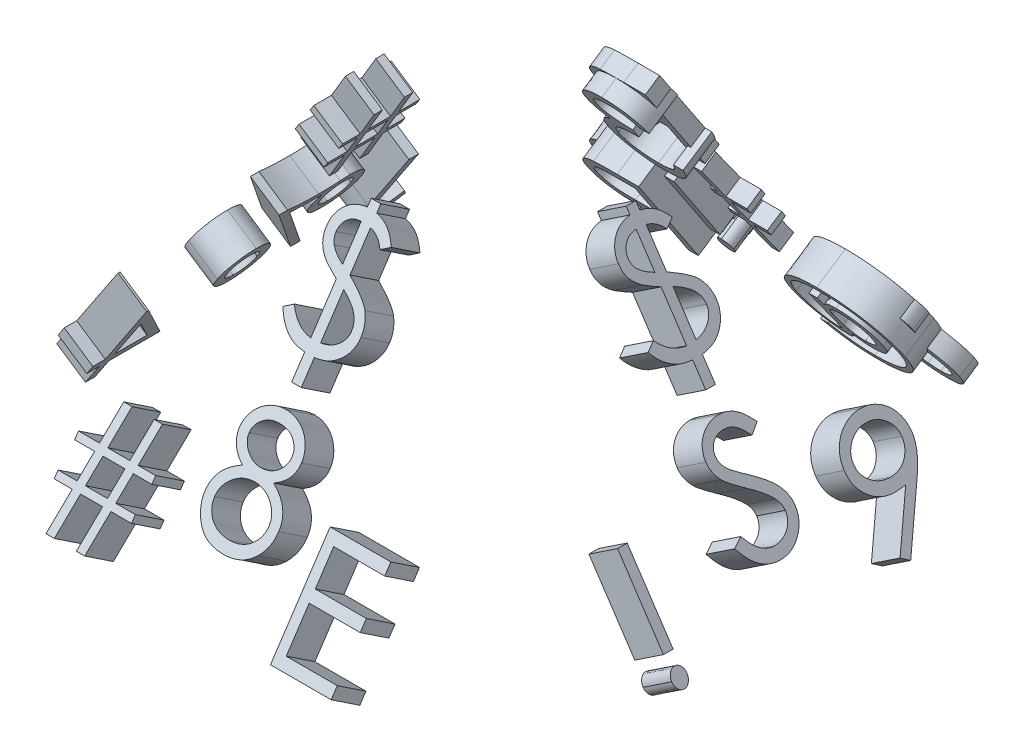
SolidWorks part; units mm, degrees
ref_plane "Front Plane" through (0, 0, 0) normal (0, 0, 1) x (1, 0, 0)
ref_plane "Top Plane" through (0, 0, 0) normal (0, 1, 0) x (1, 0, 0)
ref_plane "Right Plane" through (0, 0, 0) normal (1, 0, 0) x (0, 0, -1)
sketch "Sketch3" plane through (0, 0, 0) normal (0, 1, 0) x (1, 0, 0)
  line L1 (-50.8, -50.8) -> (50.8, -50.8)
  line L2 (-50.8, -50.8) -> (-50.8, 50.8)
  line L3 (-50.8, 50.8) -> (50.8, 50.8)
  line L4 (50.8, -50.8) -> (50.8, 50.8)
  line L5 (-50.8, -50.8) -> (50.8, 50.8) construction
  line L6 (-50.8, 50.8) -> (50.8, -50.8) construction
  point P0 (0, 0)
  dimension "D1" = 101.6
  dimension "D2" = 101.6
ref_plane "Plane4" through (0, 76.2, 0) normal (0, 1, 0) x (1, 0, 0)
sketch "Sketch4" plane through (0, 76.2, 0) normal (0, 1, 0) x (1, 0, 0)
  point P0 (0, 0)
loft "Loft1" add profiles "Sketch4", "Sketch3"
sketch "Sketch7" plane through (0, 23.4462, -35.1692) normal (0, 0.5547, -0.8321) x (-1, 0, 0)
  line L0 (-31.3891, -16.7488) -> (31.3891, -16.7488) construction
  line L1 (31.3891, -16.7488) -> (0, 39.8387) construction
  line L2 (0, 39.8387) -> (-31.3891, -16.7488) construction
  line L3 (0, 63.4022) -> (-50.8, -28.1788) construction
  line L4 (0, 63.4022) -> (50.8, -28.1788) construction
  line L5 (-50.8, -28.1788) -> (50.8, -28.1788) construction
  text T0 "R" font "Century Gothic" height in points 60
  text T1 "9" font "Century Gothic" height in points 60
  text T2 "&" font "Century Gothic" height in points 60
  text T3 "#" font "Century Gothic" height in points 60
  point P21 (0, 0)
  dimension "D1" = 11.43
  dimension "D2" = 11.43
  dimension "D3" = 11.43
  dimension "D4" = 22.86
  dimension "D5" = 6.35
  dimension "D6" = 0
  dimension "D7" = 17.78
  dimension "D8" = 0
  dimension "D9" = 4.318
  dimension "D10" = 3.81
  dimension "D11" = 7.62
shell "Shell2" thickness 2.54 removed face at (0, 0, 0)
sketch "Sketch8" plane through (0, 0, 0) normal (0, -1, 0) x (1, 0, 0)
  line L1 (47.7473, -47.7473) -> (-47.7473, -47.7473)
  line L2 (47.7473, -47.7473) -> (47.7473, 47.7473)
  line L3 (47.7473, 47.7473) -> (-47.7473, 47.7473)
  line L4 (-47.7473, -47.7473) -> (-47.7473, 47.7473)
extrude "Boss-Extrude1" add sketch "Sketch8" against normal blind 2.54
sketch "Sketch9" plane through (0, 23.4462, -35.1692) normal (0, 0.5547, -0.8321) x (-1, 0, 0)
  line L0 (-50.8, -28.1788) -> (50.8, -28.1788) construction
  circle A0 centre (35.4584, -19.2888) radius 5.715
  dimension "D1" = 11.43
  dimension "D2" = 8.89
  dimension "D3" = 15.3416
extrude "Cut-Extrude1" cut sketch "Sketch9" against normal blind 2.54
extrude "lable_1_4.1" add sketch "Sketch7" along normal blind 2.54 and the other way blind 2.54
sketch "Sketch10" plane through (0, 23.4462, -35.1692) normal (0, 0.5547, -0.8321) x (-1, 0, 0)
  line L3 (0, 63.4022) -> (-50.8, -28.1788)
  line L4 (-50.8, -28.1788) -> (50.8, -28.1788)
  line L5 (50.8, -28.1788) -> (0, 63.4022)
  line L6 (0, 63.4022) -> (-50.8, -28.1788)
  line L7 (-50.8, -28.1788) -> (50.8, -28.1788)
  line L8 (50.8, -28.1788) -> (0, 63.4022)
  dimension "D1" = 0
extrude "Cut-Extrude2" cut sketch "Sketch10" against normal through all draft 20 draft outward yes
sketch "Sketch15" plane through (-35.1692, 23.4462, 0) normal (-0.8321, 0.5547, 0) x (0, 0, 1)
  line L0 (-31.3891, -16.7488) -> (31.3891, -16.7488) construction
  line L1 (31.3891, -16.7488) -> (0, 39.8387) construction
  line L2 (0, 39.8387) -> (-31.3891, -16.7488) construction
  line L4 (-50.8, -28.1788) -> (50.8, -28.1788) construction
  line L5 (0, 63.4022) -> (50.8, -28.1788) construction
  line L6 (0, 63.4022) -> (-50.8, -28.1788) construction
  text T0 "O" font "Century Gothic" height in points 60
  text T1 "#" font "Century Gothic" height in points 60
  text T2 "9" font "Century Gothic" height in points 60
  text T3 "&" font "Century Gothic" height in points 60
  point P14 (0, 0)
  dimension "D1" = 11.43
  dimension "D2" = 11.43
  dimension "D3" = 11.43
  dimension "D4" = 21.59
  dimension "D5" = 8.382
  dimension "D6" = 23.622
  dimension "D7" = 0
  dimension "D8" = 4.064
  dimension "D9" = 6.096
  dimension "D10" = 3.048
extrude "lable_1_1" [suppressed] add sketch "Sketch15" along normal blind 2.54 and the other way blind 2.54
sketch "Sketch16" plane through (0, 23.4462, 35.1692) normal (0, 0.5547, 0.8321) x (1, 0, 0)
  line L6 (0, 39.8387) -> (-31.3891, -16.7488)
  line L7 (-31.3891, -16.7488) -> (31.3891, -16.7488)
  line L8 (31.3891, -16.7488) -> (0, 39.8387)
  line L9 (0, 39.8387) -> (-31.3891, -16.7488) construction
  line L10 (-31.3891, -16.7488) -> (31.3891, -16.7488) construction
  line L11 (31.3891, -16.7488) -> (0, 39.8387) construction
  text T0 "S" font "Century Gothic" height in points 60
  text T1 "&" font "Century Gothic" height in points 60
  text T2 "#" font "Century Gothic" height in points 60
  text T3 "9" font "Century Gothic" height in points 60
  dimension "D1" = 11.43
extrude "lable_1_2" [suppressed] add sketch "Sketch16" along normal blind 2.54 and the other way blind 2.54
sketch "Sketch17" plane through (35.1692, 23.4462, 0) normal (0.8321, 0.5547, 0) x (0, 0, -1)
  line L6 (0, 39.8387) -> (-31.3891, -16.7488)
  line L7 (-31.3891, -16.7488) -> (31.3891, -16.7488)
  line L8 (31.3891, -16.7488) -> (0, 39.8387)
  line L9 (0, 39.8387) -> (-31.3891, -16.7488) construction
  line L10 (-31.3891, -16.7488) -> (31.3891, -16.7488) construction
  line L11 (31.3891, -16.7488) -> (0, 39.8387) construction
  text T0 "E" font "Century Gothic" height in points 60
  text T1 "&" font "Century Gothic" height in points 60
  text T2 "#" font "Century Gothic" height in points 60
  text T3 "9" font "Century Gothic" height in points 60
  dimension "D1" = 11.43
extrude "lable_1_3" [suppressed] add sketch "Sketch17" along normal blind 2.54 and the other way blind 2.54
sketch "Sketch20" [suppressed] plane through (0, 23.4462, -35.1692) normal (0, 0.5547, -0.8321) x (-1, 0, 0)
  line L0 (-15.1966, -12.4684) -> (-16.7867, -10.8465) construction
  line L1 (-16.7867, -10.8465) -> (-19.1781, -8.3343) construction
  line L2 (-15.292, -14.3192) -> (-12.907, -16.7488) construction
  line L3 (-12.907, -16.7488) -> (-10.9925, -16.7488) construction
  line L4 (-12.3027, -11.8896) -> (-13.2027, -10.8465) construction
  line L5 (17.6796, -17.1558) -> (22.5674, -10.007) construction
  line L6 (20.9551, -9.9116) -> (16.5411, -16.364) construction
  line L7 (16.5411, -16.364) -> (17.6796, -17.1558) construction
  line L8 (5.8127, 2.7028) -> (2.9315, 2.7028) construction
  line L9 (2.9315, 2.7028) -> (3.4785, 6.3663) construction
  line L10 (3.4785, 6.3663) -> (6.2197, 6.3663) construction
  line L11 (6.2197, 6.3663) -> (6.2197, 7.3839) construction
  line L12 (6.2197, 7.3839) -> (3.6312, 7.3839) construction
  line L13 (3.6312, 7.3839) -> (4.3944, 12.4721) construction
  line L14 (4.3944, 12.4721) -> (3.1669, 12.4721) construction
  line L15 (3.1669, 12.4721) -> (2.4036, 7.3839) construction
  line L16 (2.4036, 7.3839) -> (-0.8464, 7.3839) construction
  line L17 (-0.8464, 7.3839) -> (-0.0832, 12.4721) construction
  line L18 (-0.0832, 12.4721) -> (-1.3107, 12.4721) construction
  line L19 (-1.3107, 12.4721) -> (-2.0739, 7.3839) construction
  line L20 (-2.0739, 7.3839) -> (-5.1777, 7.3839) construction
  line L21 (-5.1777, 7.3839) -> (-5.1777, 6.3663) construction
  line L22 (-5.1777, 6.3663) -> (-2.2266, 6.3663) construction
  line L23 (-2.2266, 6.3663) -> (-2.7767, 2.7028) construction
  line L24 (-2.7767, 2.7028) -> (-5.5847, 2.7028) construction
  line L25 (-5.5847, 2.7028) -> (-5.5847, 1.6852) construction
  line L26 (-5.5847, 1.6852) -> (-2.9294, 1.6852) construction
  line L27 (-2.9294, 1.6852) -> (-3.753, -3.81) construction
  line L28 (-3.753, -3.81) -> (-2.5223, -3.81) construction
  line L29 (-2.5223, -3.81) -> (-1.6987, 1.6852) construction
  line L30 (-1.6987, 1.6852) -> (1.5482, 1.6852) construction
  line L31 (1.5482, 1.6852) -> (0.7246, -3.81) construction
  line L32 (0.7246, -3.81) -> (1.9552, -3.81) construction
  line L33 (1.9552, -3.81) -> (2.7789, 1.6852) construction
  line L34 (2.7789, 1.6852) -> (5.8127, 1.6852) construction
  line L35 (5.8127, 1.6852) -> (5.8127, 2.7028) construction
  line L36 (-4.3147, 32.8537) -> (-4.3147, 16.9787) construction
  line L37 (-4.3147, 16.9787) -> (-2.8901, 16.9787) construction
  line L38 (-2.8901, 16.9787) -> (-2.8901, 24.3056) construction
  line L39 (-2.8901, 24.3056) -> (-1.7325, 24.3056) construction
  line L40 (-1.7325, 24.3056) -> (4.0998, 16.9787) construction
  line L41 (4.0998, 16.9787) -> (5.8615, 16.9787) construction
  line L42 (5.8615, 16.9787) -> (0.0293, 24.3056) construction
  line L43 (-1.1378, 32.8537) -> (-4.3147, 32.8537) construction
  line L44 (-15.1966, -12.4684) -> (-16.7867, -10.8465)
  line L45 (-16.7867, -10.8465) -> (-19.1781, -8.3343)
  line L46 (-15.292, -14.3192) -> (-12.907, -16.7488)
  line L47 (-12.907, -16.7488) -> (-10.9925, -16.7488)
  line L48 (-12.3027, -11.8896) -> (-13.2027, -10.8465)
  line L49 (17.6796, -17.1558) -> (22.5674, -10.007)
  line L50 (20.9551, -9.9116) -> (16.5411, -16.364)
  line L51 (16.5411, -16.364) -> (17.6796, -17.1558)
  line L52 (5.8127, 2.7028) -> (2.9315, 2.7028)
  line L53 (2.9315, 2.7028) -> (3.4785, 6.3663)
  line L54 (3.4785, 6.3663) -> (6.2197, 6.3663)
  line L55 (6.2197, 6.3663) -> (6.2197, 7.3839)
  line L56 (6.2197, 7.3839) -> (3.6312, 7.3839)
  line L57 (3.6312, 7.3839) -> (4.3944, 12.4721)
  line L58 (4.3944, 12.4721) -> (3.1669, 12.4721)
  line L59 (3.1669, 12.4721) -> (2.4036, 7.3839)
  line L60 (2.4036, 7.3839) -> (-0.8464, 7.3839)
  line L61 (-0.8464, 7.3839) -> (-0.0832, 12.4721)
  line L62 (-0.0832, 12.4721) -> (-1.3107, 12.4721)
  line L63 (-1.3107, 12.4721) -> (-2.0739, 7.3839)
  line L64 (-2.0739, 7.3839) -> (-5.1777, 7.3839)
  line L65 (-5.1777, 7.3839) -> (-5.1777, 6.3663)
  line L66 (-5.1777, 6.3663) -> (-2.2266, 6.3663)
  line L67 (-2.2266, 6.3663) -> (-2.7767, 2.7028)
  line L68 (-2.7767, 2.7028) -> (-5.5847, 2.7028)
  line L69 (-5.5847, 2.7028) -> (-5.5847, 1.6852)
  line L70 (-5.5847, 1.6852) -> (-2.9294, 1.6852)
  line L71 (-2.9294, 1.6852) -> (-3.753, -3.81)
  line L72 (-3.753, -3.81) -> (-2.5223, -3.81)
  line L73 (-2.5223, -3.81) -> (-1.6987, 1.6852)
  line L74 (-1.6987, 1.6852) -> (1.5482, 1.6852)
  line L75 (1.5482, 1.6852) -> (0.7246, -3.81)
  line L76 (0.7246, -3.81) -> (1.9552, -3.81)
  line L77 (1.9552, -3.81) -> (2.7789, 1.6852)
  line L78 (2.7789, 1.6852) -> (5.8127, 1.6852)
  line L79 (5.8127, 1.6852) -> (5.8127, 2.7028)
  line L80 (-4.3147, 32.8537) -> (-4.3147, 16.9787)
  line L81 (-4.3147, 16.9787) -> (-2.8901, 16.9787)
  line L82 (-2.8901, 16.9787) -> (-2.8901, 24.3056)
  line L83 (-2.8901, 24.3056) -> (-1.7325, 24.3056)
  line L84 (-1.7325, 24.3056) -> (4.0998, 16.9787)
  line L85 (4.0998, 16.9787) -> (5.8615, 16.9787)
  line L86 (5.8615, 16.9787) -> (0.0293, 24.3056)
  line L87 (-1.1378, 32.8537) -> (-4.3147, 32.8537)
  line L88 (-16.262, -13.3334) -> (-18.8092, -10.7352) construction
  line L89 (-1.546, 2.7028) -> (1.7008, 2.7028) construction
  line L90 (1.7008, 2.7028) -> (2.251, 6.3663) construction
  line L91 (2.251, 6.3663) -> (-0.9991, 6.3663) construction
  line L92 (-0.9991, 6.3663) -> (-1.546, 2.7028) construction
  line L93 (0.0865, 31.2255) -> (-2.8901, 31.2255) construction
  line L94 (-2.8901, 31.2255) -> (-2.8901, 25.9338) construction
  line L95 (-2.8901, 25.9338) -> (0.0165, 25.9116) construction
  line L96 (-16.262, -13.3334) -> (-18.8092, -10.7352)
  line L97 (-1.546, 2.7028) -> (1.7008, 2.7028)
  line L98 (1.7008, 2.7028) -> (2.251, 6.3663)
  line L99 (2.251, 6.3663) -> (-0.9991, 6.3663)
  line L100 (-0.9991, 6.3663) -> (-1.546, 2.7028)
  line L101 (0.0865, 31.2255) -> (-2.8901, 31.2255)
  line L102 (-2.8901, 31.2255) -> (-2.8901, 25.9338)
  line L103 (-2.8901, 25.9338) -> (0.0165, 25.9116)
  spline S0 degree 3 poles (-1211.016, 1589.987) (37.766, 13.4921) (7.6344, 6.2742) (-14.1134, -11.5897) (-53.1946, -43.2278) (-85.728, -82.5813) (-1389.1326, 1438.1841) knots -32.138305 -32.138305 -32.138305 -32.138305 0.211979 0.448506 0.7115 58.901746 58.901746 58.901746 58.901746 only from (-13.2027, -10.8465) to (-15.1966, -12.4684) construction
  spline S1 degree 3 poles (1213.8222, -1582.7079) (-59.2714, -14.9852) (-32.1987, -19.4765) (-18.3945, -7.68) (-18.0524, -7.3699) (-17.7457, -7.0763) (-17.4726, -6.7989) (-17.2383, -6.5365) (-17.0382, -6.2896) (-16.823, -5.988) (-16.6097, -5.6247) (-16.4256, -5.1931) (-14.3902, 1.855) (-54.3612, 14.9464) (1965.0086, -276.0147) knots -10.451764 -10.451764 -10.451764 -10.451764 0.105642 0.203981 0.294597 0.378912 0.455227 0.524996 0.587023 0.643258 0.744199 0.835566 0.920643 5.054796 5.054796 5.054796 5.054796 only from (-19.1781, -8.3343) to (-16.2842, -4.3623) construction
  spline S2 degree 3 poles (1973.7793, 194.0657) (-51.4849, -21.917) (-14.7602, -10.7247) (-16.381, -3.6302) (-16.5173, -3.2786) (-16.7047, -2.9408) (-16.9387, -2.6211) (-17.2268, -2.3363) (-17.559, -2.0826) (-17.9391, -1.8731) (-18.3484, -1.6979) (-18.7863, -1.5731) (-28.3709, -0.0333) (-40.7081, -35.3731) (109.6458, 1994.1865) knots -4.132886 -4.132886 -4.132886 -4.132886 0.074197 0.148047 0.222587 0.300557 0.37994 0.460256 0.543595 0.630739 0.720813 0.811094 0.904147 6.547345 6.547345 6.547345 6.547345 only from (-16.2842, -4.3623) to (-19.7187, -1.4843) construction
  spline S3 degree 3 poles (-96.2047, 1996.9105) (-1.1162, -30.4751) (-11.5215, -0.5018) (-20.4569, -1.5327) (-20.8041, -1.6037) (-21.1379, -1.6965) (-21.4523, -1.828) (-21.7571, -1.974) (-28.7123, -6.4707) (-17.3542, -34.8268) (-1252.8823, 1574.128) knots -9.254206 -9.254206 -9.254206 -9.254206 0.135626 0.266321 0.392983 0.516276 0.637901 0.758631 0.879017 9.511566 9.511566 9.511566 9.511566 only from (-19.7187, -1.4843) to (-22.3041, -2.3684) construction
  spline S4 degree 3 poles (-1373.4615, 1472.0964) (6.456, -12.0068) (-17.6213, 2.8205) (-22.7023, -2.7663) (-22.8532, -2.9916) (-22.984, -3.225) (-23.0817, -3.4736) (-23.1511, -3.734) (-24.2565, -10.0188) (7.5119, -18.9958) (-2017.4492, 146.1379) knots -9.92722 -9.92722 -9.92722 -9.92722 0.131449 0.257906 0.381113 0.501946 0.623787 0.745627 0.870676 9.333997 9.333997 9.333997 9.333997 only from (-22.3041, -2.3684) to (-23.2041, -4.286) construction
  spline S5 degree 3 poles (-2015.3815, -179.3604) (8.1381, 12.7979) (-24.523, 2.2958) (-23.123, -4.9748) (-23.0129, -5.329) (-22.8872, -5.632) (-22.7505, -5.8874) (-22.6249, -6.1097) (-22.4672, -6.3547) (-22.2813, -6.6244) (-22.0732, -6.9226) (-21.8364, -7.2447) (-11.1832, -21.2383) (14.4163, -23.4182) (-1566.5908, -1277.2192) knots -4.999634 -4.999634 -4.999634 -4.999634 0.080148 0.163016 0.250603 0.343925 0.395896 0.456723 0.525583 0.60322 0.689875 0.784341 0.887706 13.206881 13.206881 13.206881 13.206881 only from (-23.2041, -4.286) to (-21.2865, -7.9526) construction
  spline S6 degree 3 poles (-1258.508, 1562.9871) (24.2351, -1.632) (-7.0336, 4.4872) (-22.3165, -8.8237) (-22.7641, -9.2371) (-23.1684, -9.6273) (-23.5183, -10.0028) (-23.829, -10.351) (-24.0821, -10.6865) (-24.3605, -11.0941) (-24.6251, -11.6) (-24.8626, -12.2056) (-27.2311, -22.2702) (15.6235, -37.4436) (-2014.3666, 191.7077) knots -8.568615 -8.568615 -8.568615 -8.568615 0.10298 0.198866 0.287721 0.369301 0.444358 0.512001 0.573159 0.6279 0.727593 0.821895 0.911698 5.220728 5.220728 5.220728 5.220728 only from (-21.2865, -7.9526) to (-25.0358, -13.4256) construction
  spline S7 degree 3 poles (-2021.6065, -128.263) (6.2867, 5.1239) (-26.1824, -5.6484) (-24.9748, -14.1887) (-24.8934, -14.5482) (-24.7742, -14.8912) (-24.6218, -15.2182) (-24.4366, -15.5285) (-24.217, -15.8206) (-23.9682, -16.0957) (-23.6901, -16.345) (-23.3888, -16.5651) (-23.0626, -16.7449) (-22.7168, -16.8957) (-22.3495, -17.0143) (-21.9592, -17.095) (-12.5827, -18.3074) (-1.1632, 14.4463) (-121.9288, -2014.4951) knots -4.067076 -4.067076 -4.067076 -4.067076 0.064496 0.126884 0.187124 0.246441 0.305977 0.36519 0.424708 0.486277 0.548235 0.609019 0.670238 0.731947 0.79524 0.860594 0.928698 5.460162 5.460162 5.460162 5.460162 only from (-25.0358, -13.4256) to (-21.1211, -17.1558) construction
  spline S8 degree 3 poles (105.4375, -2012.9623) (-46.4777, 21.2594) (-31.562, -18.9943) (-19.8205, -17.028) (-19.1948, -16.8473) (-18.6812, -16.6419) (-18.2652, -16.4305) (-17.923, -16.2343) (-17.554, -16.0024) (-17.1543, -15.7376) (-16.7283, -15.4348) (-16.2759, -15.0935) (-0.8159, -3.2749) (-0.512, 27.4826) (1265.8678, -1549.7318) knots -5.076743 -5.076743 -5.076743 -5.076743 0.099479 0.19723 0.295054 0.393883 0.447109 0.506216 0.572397 0.644405 0.723232 0.808942 0.900994 9.532577 9.532577 9.532577 9.532577 only from (-21.1211, -17.1558) to (-15.292, -14.3192) construction
  spline S9 degree 3 poles (1466.2951, 1330.8092) (10.7971, -58.9757) (4.6752, -32.6363) (-11.6795, -16.046) (-46.1587, 19.0578) (-86.0822, 48.5893) (1308.3834, 1484.0297) knots -33.089565 -33.089565 -33.089565 -33.089565 0.227433 0.471173 0.72797 71.654968 71.654968 71.654968 71.654968 only from (-10.9925, -16.7488) to (-12.4395, -15.2732) construction
  spline S10 degree 3 poles (1478.6723, 1316.367) (21.6085, -71.1392) (9.5912, -37.4776) (-13.3896, -14.3089) (-33.2104, 6.0641) (-62.8373, 16.5022) (1352.8811, 1445.4489) knots -37.612235 -37.612235 -37.612235 -37.612235 0.277779 0.537034 0.77778 33.71632 33.71632 33.71632 33.71632 only from (-12.4395, -15.2732) to (-14.2267, -13.4542) construction
  spline S11 degree 3 poles (-1341.9172, 1481.3358) (-50.1448, -60.2796) (-36.1748, -31.1825) (-13.2966, -12.6979) (27.3008, 20.3634) (73.138, 46.6573) (-1148.1149, 1631.7199) knots -34.846163 -34.846163 -34.846163 -34.846163 0.235134 0.479473 0.735631 63.573763 63.573763 63.573763 63.573763 only from (-14.2267, -13.4542) to (-12.3027, -11.8896) construction
  spline S12 degree 3 poles (1668.2044, -1146.2833) (-10.7043, -24.0989) (14.6997, -22.3807) (23.0413, -9.2835) (23.2502, -8.9385) (23.4351, -8.6061) (23.6071, -8.2897) (23.7545, -7.9854) (23.8874, -7.6962) (24.0286, -7.3301) (24.1749, -6.8869) (24.3038, -6.3632) (25.8363, 4.0048) (-8.4285, 16.8712) (2020.7141, -124.8402) knots -8.910329 -8.910329 -8.910329 -8.910329 0.087946 0.171747 0.250583 0.32591 0.396143 0.462994 0.525418 0.583838 0.694397 0.800583 0.90168 6.863836 6.863836 6.863836 6.863836 only from (22.5674, -10.007) to (24.3959, -5.345) construction
  spline S13 degree 3 poles (2017.2359, 161.6488) (-15.7997, -30.0858) (26.4308, -14.9769) (24.2462, -4.0769) (24.0418, -3.4701) (23.7584, -2.8888) (23.4055, -2.3477) (22.9865, -1.8624) (22.5022, -1.4445) (21.9636, -1.0938) (21.3819, -0.814) (20.7699, -0.6115) (9.3934, 1.527) (-5.7744, -39.9197) (169.9675, 1993.6962) knots -4.058346 -4.058346 -4.058346 -4.058346 0.083474 0.165402 0.248081 0.332 0.416297 0.498735 0.580591 0.664318 0.748057 0.830997 0.914468 5.233291 5.233291 5.233291 5.233291 only from (24.3959, -5.345) to (19.4763, -0.4667) construction
  spline S14 degree 3 poles (-127.7649, 1993.9185) (44.9609, -40.2134) (29.6793, 1.5495) (18.1496, -0.6145) (17.5161, -0.8243) (16.9113, -1.1088) (16.3516, -1.4626) (15.8504, -1.8742) (15.419, -2.3441) (15.0601, -2.8658) (14.7751, -3.4318) (14.5708, -4.034) (12.3869, -15.2278) (54.9701, -30.4623) (-1979.29, 151.7815) knots -4.230904 -4.230904 -4.230904 -4.230904 0.086062 0.17094 0.255778 0.341735 0.427007 0.509416 0.590092 0.671171 0.751825 0.832673 0.914751 5.113135 5.113135 5.113135 5.113135 only from (19.4763, -0.4667) to (14.4232, -5.3291) construction
  spline S15 degree 3 poles (-1982.2681, -117.5572) (47.9002, 15.9969) (13.054, 3.6541) (14.5041, -6.2813) (14.6155, -6.7306) (14.7685, -7.1623) (14.9702, -7.5716) (15.213, -7.9642) (15.5053, -8.3323) (15.8332, -8.6801) (16.1939, -8.9969) (16.5785, -9.2736) (16.9829, -9.5088) (17.4066, -9.6985) (17.8487, -9.8511) (18.3108, -9.9534) (28.6348, -11.379) (41.3764, 22.9838) (-94.5785, -2006.6302) knots -3.797348 -3.797348 -3.797348 -3.797348 0.064609 0.12725 0.188534 0.248578 0.309139 0.369772 0.431966 0.495825 0.559795 0.622662 0.68409 0.74564 0.807138 0.869869 0.933705 4.947275 4.947275 4.947275 4.947275 only from (14.4232, -5.3291) to (19.2855, -10.0324) construction
  spline S16 degree 3 poles (119.0292, -2007.3224) (-12.2834, 26.9885) (23.1112, -49.516) (47.1443, 32.0919) (208.2591, -2000.898) knots -26.084625 -26.084625 -26.084625 -26.084625 0.492142 27.359519 27.359519 27.359519 27.359519 only from (19.2855, -10.0324) to (20.9551, -9.9116) construction
  spline S17 degree 3 poles (13.5867, -1975.4638) (-27.7179, 48.4127) (-13.0892, 23.5705) (0.9903, 24.337) (1.4338, 24.3781) (1.85, 24.4341) (2.2379, 24.5083) (2.5993, 24.5911) (2.9306, 24.6983) (3.3329, 24.8507) (3.7885, 25.0886) (4.2778, 25.4317) (4.6965, 25.8417) (5.045, 26.3085) (5.3186, 26.8263) (5.5171, 27.385) (7.6544, 37.9462) (-35.3403, 52.6149) (1999.1094, -131.0337) knots -5.078847 -5.078847 -5.078847 -5.078847 0.062052 0.120621 0.175789 0.228041 0.2771 0.323011 0.366127 0.406783 0.483311 0.556994 0.62881 0.700809 0.773286 0.846279 0.92122 4.77063 4.77063 4.77063 4.77063 only from (0.0293, 24.3056) to (5.658, 28.6083) construction
  spline S18 degree 3 poles (2003.9003, 109.732) (-23.2225, 9.7328) (6.6402, 20.3137) (5.6096, 29.3548) (5.5396, 29.7081) (5.4404, 30.0449) (5.3172, 30.3683) (5.1624, 30.6752) (4.9828, 30.9687) (4.7699, 31.2401) (4.5441, 31.4988) (4.2939, 31.7306) (4.0294, 31.9414) (3.7494, 32.1299) (3.451, 32.2931) (3.1357, 32.4319) (-4.8385, 35.3242) (-21.5091, 8.2328) (543.2062, 1958.0336) knots -4.680958 -4.680958 -4.680958 -4.680958 0.068359 0.134815 0.198683 0.261561 0.323202 0.38431 0.445928 0.507648 0.56935 0.630173 0.690547 0.750868 0.811255 0.872936 0.935783 5.359963 5.359963 5.359963 5.359963 only from (5.658, 28.6083) to (2.4588, 32.6374) construction
  spline S19 degree 3 poles (378.3496, 1996.9387) (13.9488, 7.4413) (10.0374, 31.6395) (1.8639, 32.7373) (1.4934, 32.7698) (1.0706, 32.8038) (0.5943, 32.8224) (0.0644, 32.8441) (-26.6805, 33.1906) (-53.1799, 16.841) (-87.9157, 2030.4344) knots -6.585191 -6.585191 -6.585191 -6.585191 0.073628 0.162615 0.265302 0.382842 0.515178 0.661566 0.823742 22.749636 22.749636 22.749636 22.749636 only from (2.4588, 32.6374) to (-1.1378, 32.8537) construction
  spline S20 degree 3 poles (-13.2027, -10.8465) (-13.3438, -10.9609) (-13.6424, -11.2028) (-14.1134, -11.5897) (-14.6381, -12.0145) (-15.0048, -12.3125) (-15.1966, -12.4684) knots 0 0 0 0 0.211979 0.448506 0.7115 1 1 1 1
  spline S21 degree 3 poles (-19.1781, -8.3343) (-19.0399, -8.2214) (-18.7729, -8.0034) (-18.3945, -7.68) (-18.0524, -7.3699) (-17.7457, -7.0763) (-17.4726, -6.7989) (-17.2383, -6.5365) (-17.0382, -6.2896) (-16.823, -5.988) (-16.6097, -5.6247) (-16.4256, -5.1931) (-16.3048, -4.7749) (-16.2909, -4.4966) (-16.2842, -4.3623) knots 0 0 0 0 0.105642 0.203981 0.294597 0.378912 0.455227 0.524996 0.587023 0.643258 0.744199 0.835566 0.920643 1 1 1 1
  spline S22 degree 3 poles (-16.2842, -4.3623) (-16.2889, -4.2389) (-16.2981, -3.9927) (-16.381, -3.6302) (-16.5173, -3.2786) (-16.7047, -2.9408) (-16.9387, -2.6211) (-17.2268, -2.3363) (-17.559, -2.0826) (-17.9391, -1.8731) (-18.3484, -1.6979) (-18.7863, -1.5731) (-19.2455, -1.4993) (-19.5594, -1.4894) (-19.7187, -1.4843) knots 0 0 0 0 0.074197 0.148047 0.222587 0.300557 0.37994 0.460256 0.543595 0.630739 0.720813 0.811094 0.904147 1 1 1 1
  spline S23 degree 3 poles (-19.7187, -1.4843) (-19.845, -1.4865) (-20.0929, -1.4907) (-20.4569, -1.5327) (-20.8041, -1.6037) (-21.1379, -1.6965) (-21.4523, -1.828) (-21.7571, -1.974) (-22.0409, -2.1575) (-22.2162, -2.298) (-22.3041, -2.3684) knots 0 0 0 0 0.135626 0.266321 0.392983 0.516276 0.637901 0.758631 0.879017 1 1 1 1
  spline S24 degree 3 poles (-22.3041, -2.3684) (-22.3751, -2.433) (-22.5145, -2.5597) (-22.7023, -2.7663) (-22.8532, -2.9916) (-22.984, -3.225) (-23.0817, -3.4736) (-23.1511, -3.734) (-23.1989, -4.0055) (-23.2023, -4.1915) (-23.2041, -4.286) knots 0 0 0 0 0.131449 0.257906 0.381113 0.501946 0.623787 0.745627 0.870676 1 1 1 1
  spline S25 degree 3 poles (-23.2041, -4.286) (-23.1994, -4.3986) (-23.1899, -4.6277) (-23.123, -4.9748) (-23.0129, -5.329) (-22.8872, -5.632) (-22.7505, -5.8874) (-22.6249, -6.1097) (-22.4672, -6.3547) (-22.2813, -6.6244) (-22.0732, -6.9226) (-21.8364, -7.2447) (-21.5725, -7.5914) (-21.3844, -7.8289) (-21.2865, -7.9526) knots 0 0 0 0 0.080148 0.163016 0.250603 0.343925 0.395896 0.456723 0.525583 0.60322 0.689875 0.784341 0.887706 1 1 1 1
  spline S26 degree 3 poles (-21.2865, -7.9526) (-21.4685, -8.1023) (-21.82, -8.3912) (-22.3165, -8.8237) (-22.7641, -9.2371) (-23.1684, -9.6273) (-23.5183, -10.0028) (-23.829, -10.351) (-24.0821, -10.6865) (-24.3605, -11.0941) (-24.6251, -11.6) (-24.8626, -12.2056) (-25.0062, -12.8158) (-25.026, -13.2235) (-25.0358, -13.4256) knots 0 0 0 0 0.10298 0.198866 0.287721 0.369301 0.444358 0.512001 0.573159 0.6279 0.727593 0.821895 0.911698 1 1 1 1
  spline S27 degree 3 poles (-25.0358, -13.4256) (-25.0332, -13.5561) (-25.028, -13.813) (-24.9748, -14.1887) (-24.8934, -14.5482) (-24.7742, -14.8912) (-24.6218, -15.2182) (-24.4366, -15.5285) (-24.217, -15.8206) (-23.9682, -16.0957) (-23.6901, -16.345) (-23.3888, -16.5651) (-23.0626, -16.7449) (-22.7168, -16.8957) (-22.3495, -17.0143) (-21.9592, -17.095) (-21.5477, -17.1482) (-21.2655, -17.1532) (-21.1211, -17.1558) knots 0 0 0 0 0.064496 0.126884 0.187124 0.246441 0.305977 0.36519 0.424708 0.486277 0.548235 0.609019 0.670238 0.731947 0.79524 0.860594 0.928698 1 1 1 1
  spline S28 degree 3 poles (-21.1211, -17.1558) (-20.9013, -17.1492) (-20.4655, -17.136) (-19.8205, -17.028) (-19.1948, -16.8473) (-18.6812, -16.6419) (-18.2652, -16.4305) (-17.923, -16.2343) (-17.554, -16.0024) (-17.1543, -15.7376) (-16.7283, -15.4348) (-16.2759, -15.0935) (-15.7901, -14.7222) (-15.462, -14.4567) (-15.292, -14.3192) knots 0 0 0 0 0.099479 0.19723 0.295054 0.393883 0.447109 0.506216 0.572397 0.644405 0.723232 0.808942 0.900994 1 1 1 1
  spline S29 degree 3 poles (-10.9925, -16.7488) (-11.1016, -16.6363) (-11.3274, -16.4032) (-11.6795, -16.046) (-12.0524, -15.6663) (-12.308, -15.4067) (-12.4395, -15.2732) knots 0 0 0 0 0.227433 0.471173 0.72797 1 1 1 1
  spline S30 degree 3 poles (-12.4395, -15.2732) (-12.6047, -15.1045) (-12.924, -14.7783) (-13.3896, -14.3089) (-13.8177, -13.8688) (-14.094, -13.5887) (-14.2267, -13.4542) knots 0 0 0 0 0.277779 0.537034 0.77778 1 1 1 1
  spline S31 degree 3 poles (-14.2267, -13.4542) (-14.0763, -13.3311) (-13.7696, -13.08) (-13.2966, -12.6979) (-12.8064, -12.2986) (-12.4724, -12.0274) (-12.3027, -11.8896) knots 0 0 0 0 0.235134 0.479473 0.735631 1 1 1 1
  spline S32 degree 3 poles (22.5674, -10.007) (22.6506, -9.8833) (22.8131, -9.6418) (23.0413, -9.2835) (23.2502, -8.9385) (23.4351, -8.6061) (23.6071, -8.2897) (23.7545, -7.9854) (23.8874, -7.6962) (24.0286, -7.3301) (24.1749, -6.8869) (24.3038, -6.3632) (24.3797, -5.8497) (24.3906, -5.5116) (24.3959, -5.345) knots 0 0 0 0 0.087946 0.171747 0.250583 0.32591 0.396143 0.462994 0.525418 0.583838 0.694397 0.800583 0.90168 1 1 1 1
  spline S33 degree 3 poles (24.3959, -5.345) (24.3879, -5.1303) (24.3721, -4.7048) (24.2462, -4.0769) (24.0418, -3.4701) (23.7584, -2.8888) (23.4055, -2.3477) (22.9865, -1.8624) (22.5022, -1.4445) (21.9636, -1.0938) (21.3819, -0.814) (20.7699, -0.6115) (20.1308, -0.4914) (19.6963, -0.475) (19.4763, -0.4667) knots 0 0 0 0 0.083474 0.165402 0.248081 0.332 0.416297 0.498735 0.580591 0.664318 0.748057 0.830997 0.914468 1 1 1 1
  spline S34 degree 3 poles (19.4763, -0.4667) (19.2522, -0.4749) (18.8069, -0.4912) (18.1496, -0.6145) (17.5161, -0.8243) (16.9113, -1.1088) (16.3516, -1.4626) (15.8504, -1.8742) (15.419, -2.3441) (15.0601, -2.8658) (14.7751, -3.4318) (14.5708, -4.034) (14.4465, -4.671) (14.431, -5.107) (14.4232, -5.3291) knots 0 0 0 0 0.086062 0.17094 0.255778 0.341735 0.427007 0.509416 0.590092 0.671171 0.751825 0.832673 0.914751 1 1 1 1
  spline S35 degree 3 poles (14.4232, -5.3291) (14.4273, -5.4915) (14.4355, -5.8114) (14.5041, -6.2813) (14.6155, -6.7306) (14.7685, -7.1623) (14.9702, -7.5716) (15.213, -7.9642) (15.5053, -8.3323) (15.8332, -8.6801) (16.1939, -8.9969) (16.5785, -9.2736) (16.9829, -9.5088) (17.4066, -9.6985) (17.8487, -9.8511) (18.3108, -9.9534) (18.7918, -10.0198) (19.1189, -10.0282) (19.2855, -10.0324) knots 0 0 0 0 0.064609 0.12725 0.188534 0.248578 0.309139 0.369772 0.431966 0.495825 0.559795 0.622662 0.68409 0.74564 0.807138 0.869869 0.933705 1 1 1 1
  spline S36 degree 3 poles (19.2855, -10.0324) (19.5604, -10.0263) (20.1189, -10.0138) (20.6734, -9.946) (20.9551, -9.9116) knots 0 0 0 0 0.492142 1 1 1 1
  spline S37 degree 3 poles (0.0293, 24.3056) (0.1957, 24.3076) (0.5193, 24.3114) (0.9903, 24.337) (1.4338, 24.3781) (1.85, 24.4341) (2.2379, 24.5083) (2.5993, 24.5911) (2.9306, 24.6983) (3.3329, 24.8507) (3.7885, 25.0886) (4.2778, 25.4317) (4.6965, 25.8417) (5.045, 26.3085) (5.3186, 26.8263) (5.5171, 27.385) (5.6383, 27.984) (5.6513, 28.3967) (5.658, 28.6083) knots 0 0 0 0 0.062052 0.120621 0.175789 0.228041 0.2771 0.323011 0.366127 0.406783 0.483311 0.556994 0.62881 0.700809 0.773286 0.846279 0.92122 1 1 1 1
  spline S38 degree 3 poles (5.658, 28.6083) (5.6558, 28.7356) (5.6516, 28.9867) (5.6096, 29.3548) (5.5396, 29.7081) (5.4404, 30.0449) (5.3172, 30.3683) (5.1624, 30.6752) (4.9828, 30.9687) (4.7699, 31.2401) (4.5441, 31.4988) (4.2939, 31.7306) (4.0294, 31.9414) (3.7494, 32.1299) (3.451, 32.2931) (3.1357, 32.4319) (2.8048, 32.552) (2.575, 32.6087) (2.4588, 32.6374) knots 0 0 0 0 0.068359 0.134815 0.198683 0.261561 0.323202 0.38431 0.445928 0.507648 0.56935 0.630173 0.690547 0.750868 0.811255 0.872936 0.935783 1 1 1 1
  spline S39 degree 3 poles (2.4588, 32.6374) (2.3721, 32.6553) (2.1805, 32.6948) (1.8639, 32.7373) (1.4934, 32.7698) (1.0706, 32.8038) (0.5943, 32.8224) (0.0644, 32.8441) (-0.5188, 32.8516) (-0.9258, 32.853) (-1.1378, 32.8537) knots 0 0 0 0 0.073628 0.162615 0.265302 0.382842 0.515178 0.661566 0.823742 1 1 1 1
  spline S40 degree 3 poles (-4007.4879, -339.752) (21.0187, 11.8601) (-22.9452, 1.5335) (-21.7337, -4.8465) (-19.471, -11.2373) (22.2736, 0.5005) (-3650.9494, -1686.4255) knots -23.051601 -23.051601 -23.051601 -23.051601 0.250262 0.500554 0.748645 25.118006 25.118006 25.118006 25.118006 only from (-21.7794, -4.4418) to (-21.5727, -5.221) construction
  spline S41 degree 3 poles (-3407.0555, -2135.0626) (3.7404, 45.9349) (-29.839, 6.3253) (-20.9593, -6.1601) (-9.0847, -21.7347) (41.1448, -6.0102) (-3092.5584, -2567.6706) knots -18.4044 -18.4044 -18.4044 -18.4044 0.220523 0.461139 0.719906 24.680055 24.680055 24.680055 24.680055 only from (-21.5727, -5.221) to (-20.1544, -7.1544) construction
  spline S42 degree 3 poles (2311.6286, -3256.7287) (-82.9132, 18.2001) (-33.4653, -17.9428) (-19.0161, -6.3174) (-8.9332, 2.6995) (-43.5815, 54.263) (2896.1544, -2744.5549) knots -20.481578 -20.481578 -20.481578 -20.481578 0.287445 0.548797 0.785479 15.772191 15.772191 15.772191 15.772191 only from (-20.1544, -7.1544) to (-18.1764, -5.4595) construction
  spline S43 degree 3 poles (3354.2529, -2155.9913) (-74.4912, 9.7306) (-22.0061, -12.8286) (-17.828, -4.9157) (-15.6403, 0.6118) (-72.834, 18.4686) (3900.5074, -807.7662) knots -22.158799 -22.158799 -22.158799 -22.158799 0.300653 0.566171 0.794353 15.40402 15.40402 15.40402 15.40402 only from (-18.1764, -5.4595) to (-17.7089, -4.41) construction
  spline S44 degree 3 poles (3892.5404, 836.1297) (-77.6925, -28.6998) (-15.3878, -9.2502) (-17.8428, -3.9039) (-18.0284, -3.6818) (-18.2782, -3.4841) (-18.5825, -3.3162) (-18.9384, -3.1951) (-30.0243, -1.3218) (-45.3963, -57.3415) (251.723, 3987.379) knots -6.139606 -6.139606 -6.139606 -6.139606 0.095564 0.192533 0.297697 0.416353 0.546125 0.68385 0.834051 13.047845 13.047845 13.047845 13.047845 only from (-17.7089, -4.41) to (-19.7728, -3.1126) construction
  spline S45 degree 3 poles (-319.3435, 3985.3903) (4.9045, -58.1892) (-10.2075, -1.2795) (-20.5738, -3.1985) (-20.9204, -3.3242) (-21.221, -3.4934) (-21.4663, -3.6967) (-21.6462, -3.9257) (-24.1078, -9.3925) (38.4496, -28.9303) (-3933.4262, 830.656) knots -11.40661 -11.40661 -11.40661 -11.40661 0.159521 0.306982 0.443331 0.57416 0.694803 0.800649 0.900947 7.341507 7.341507 7.341507 7.341507 only from (-19.7728, -3.1126) to (-21.7794, -4.4418) construction
  spline S46 degree 3 poles (-2914.6554, -2769.3346) (32.4941, -20.4599) (-5.0563, -26.0142) (-19.4967, -9.9895) (-36.7706, 9.0889) (-29.9572, 49.3615) (-3058.1823, -2610.3538) knots -29.462481 -29.462481 -29.462481 -29.462481 0.225658 0.468256 0.725626 36.24397 36.24397 36.24397 36.24397 only from (-18.8092, -10.7352) to (-20.2466, -9.1452) construction
  spline S47 degree 3 poles (-2432.243, 3181.1103) (38.5027, -10.1891) (-2.9013, 4.8674) (-21.1825, -9.8782) (-21.5924, -10.2174) (-21.9535, -10.5416) (-22.2721, -10.8434) (-22.5488, -11.1229) (-22.7772, -11.3861) (-23.0187, -11.7) (-23.2492, -12.0767) (-23.4537, -12.5176) (-26.1436, -21.3307) (36.7408, -40.4641) (-3977.1619, 592.2831) knots -12.343017 -12.343017 -12.343017 -12.343017 0.112416 0.216427 0.311718 0.399092 0.477875 0.548155 0.610915 0.665521 0.761427 0.848075 0.927081 5.687326 5.687326 5.687326 5.687326 only from (-20.2466, -9.1452) to (-23.6111, -13.362) construction
  spline S48 degree 3 poles (-4014.6835, -277.0646) (17.1384, 4.294) (-24.7229, -6.2646) (-23.5684, -13.8165) (-23.5062, -14.0344) (-23.4238, -14.2462) (-23.3144, -14.4507) (-23.1808, -14.6477) (-23.0219, -14.836) (-22.8469, -15.0193) (-22.6521, -15.1872) (-22.4398, -15.3295) (-22.2206, -15.4545) (-21.9903, -15.5585) (-21.7469, -15.6323) (-21.4957, -15.692) (-12.0249, -16.7848) (-0.6671, 23.1014) (-185.6078, -4012.0872) knots -5.625249 -5.625249 -5.625249 -5.625249 0.058197 0.11618 0.173161 0.230409 0.288896 0.349333 0.411228 0.476294 0.542121 0.606588 0.670554 0.734141 0.798462 0.863852 0.930519 8.04058 8.04058 8.04058 8.04058 only from (-23.6111, -13.362) to (-20.9621, -15.7311) construction
  spline S49 degree 3 poles (318.763, -4001.0465) (-46.3314, 38.4152) (-30.6122, -17.5157) (-20.1232, -15.6447) (-9.3835, -12.7401) (-18.1313, 44.5558) (1350.68, -3773.152) knots -17.932087 -17.932087 -17.932087 -17.932087 0.246277 0.493763 0.743289 19.755825 19.755825 19.755825 19.755825 only from (-20.9621, -15.7311) to (-19.3085, -15.3623) construction
  spline S50 degree 3 poles (1776.0355, -3589.2753) (-59.3512, 11.2831) (-29.2411, -21.0059) (-18.6317, -15.0116) (-18.272, -14.8012) (-17.9007, -14.5571) (-17.5126, -14.29) (-17.108, -13.9972) (1.8101, 0.5194) (0.215, 40.6685) (2521.2433, -3104.5552) knots -9.638895 -9.638895 -9.638895 -9.638895 0.099233 0.205135 0.318994 0.439914 0.568292 0.704211 0.848264 20.063042 20.063042 20.063042 20.063042 only from (-19.3085, -15.3623) to (-16.262, -13.3334) construction
  spline S51 degree 3 poles (-167.1494, 3993.3881) (43.6699, -45.4346) (29.9783, -0.8354) (18.6954, -2.146) (18.3604, -2.2201) (18.0377, -2.3218) (17.728, -2.453) (17.4315, -2.6118) (17.1499, -2.8013) (16.8861, -3.0163) (16.6407, -3.248) (16.4315, -3.501) (16.2519, -3.7624) (16.1028, -4.0356) (15.9894, -4.3222) (15.9049, -4.6201) (14.4817, -13.8338) (62.9827, -26.4754) (-3975.7545, 250.0212) knots -6.241342 -6.241342 -6.241342 -6.241342 0.068712 0.134812 0.199538 0.263335 0.326747 0.390328 0.454126 0.519203 0.58351 0.645497 0.70529 0.763488 0.821856 0.880004 0.939108 6.100925 6.100925 6.100925 6.100925 only from (19.4032, -2.0949) to (15.8479, -5.2496) construction
  spline S52 degree 3 poles (-3973.6923, -289.6474) (64.979, 15.7615) (14.42, 2.9683) (15.9083, -5.8792) (15.9957, -6.1771) (16.1129, -6.4651) (16.2671, -6.7403) (16.4563, -7.0014) (16.6781, -7.2514) (16.9296, -7.4864) (17.2048, -7.7021) (17.4987, -7.8904) (17.8062, -8.0495) (18.1285, -8.1771) (18.4632, -8.2797) (18.8133, -8.3531) (30.5581, -9.6623) (44.6635, 34.691) (-163.0895, -4003.9514) knots -4.791055 -4.791055 -4.791055 -4.791055 0.05954 0.117423 0.17444 0.231734 0.289722 0.3492 0.410516 0.47508 0.540094 0.604444 0.668697 0.73211 0.796739 0.862906 0.930462 7.350564 7.350564 7.350564 7.350564 only from (15.8479, -5.2496) to (19.5495, -8.4042) construction
  spline S53 degree 3 poles (209.2268, -4003.5922) (-5.4422, 35.5627) (8.6646, -9.6717) (20.2815, -8.3532) (20.6214, -8.2807) (20.9419, -8.1768) (21.2464, -8.0513) (21.5299, -7.8916) (21.7928, -7.7011) (22.0368, -7.4869) (22.2534, -7.249) (22.4464, -7) (22.6104, -6.7388) (22.7399, -6.4622) (22.8465, -6.1768) (22.92, -5.8781) (24.2319, 4.1164) (-20.2938, 16.9886) (4016.1405, -235.5027) knots -6.514699 -6.514699 -6.514699 -6.514699 0.072713 0.141547 0.208363 0.272462 0.33539 0.397711 0.459383 0.522098 0.584315 0.644392 0.703345 0.761509 0.82003 0.878517 0.938265 6.613688 6.613688 6.613688 6.613688 only from (19.5495, -8.4042) to (22.9713, -5.2496) construction
  spline S54 degree 3 poles (4014.6342, 249.6522) (-24.1621, -26.4716) (24.3373, -13.8343) (22.9142, -4.6201) (22.8297, -4.3222) (22.7164, -4.0355) (22.5671, -3.7626) (22.3879, -3.4999) (22.175, -3.2491) (21.9301, -3.0161) (21.6659, -2.8013) (21.3844, -2.6118) (21.0879, -2.453) (20.7782, -2.3219) (20.4546, -2.2196) (20.1173, -2.146) (8.7473, -0.8341) (-5.0513, -45.4824) (207.272, 3993.2843) knots -5.090082 -5.090082 -5.090082 -5.090082 0.06076 0.119735 0.177757 0.235999 0.29407 0.353733 0.415973 0.48014 0.545076 0.608735 0.672178 0.735453 0.799112 0.864284 0.930837 7.275581 7.275581 7.275581 7.275581 only from (22.9713, -5.2496) to (19.4032, -2.0949) construction
  spline S55 degree 3 poles (3981.5161, 450.9942) (-52.9008, 4.6669) (6.2611, 20.41) (4.1289, 29.3625) (3.9797, 29.712) (3.7787, 30.0393) (3.5337, 30.3365) (3.2465, 30.5907) (2.9249, 30.8004) (2.6243, 30.9345) (2.3557, 31.0167) (2.1224, 31.0745) (1.8588, 31.121) (1.5637, 31.1582) (1.2382, 31.1902) (0.8807, 31.2118) (-16.4472, 31.7831) (-34.1438, -1.4674) (6.8999, 4030.8973) knots -4.727484 -4.727484 -4.727484 -4.727484 0.068814 0.136365 0.204019 0.273064 0.342913 0.410965 0.479169 0.549308 0.587652 0.630647 0.678879 0.731934 0.791111 0.855283 0.925086 10.142584 10.142584 10.142584 10.142584 only from (4.2333, 28.6114) to (0.0865, 31.2255) construction
  spline S56 degree 3 poles (46.0928, -3973.4969) (-29.4536, 63.6629) (-13.9513, 25.2275) (0.7958, 25.9295) (1.1502, 25.9501) (1.4769, 25.9816) (1.7763, 26.0222) (2.048, 26.0731) (2.2926, 26.1323) (2.5779, 26.2239) (2.8965, 26.3691) (3.2427, 26.5803) (3.5375, 26.8459) (3.7866, 27.1497) (3.9868, 27.4837) (4.1279, 27.8439) (6.2822, 36.9217) (-53.4741, 53.1891) (3979.1595, -414.3294) knots -7.595162 -7.595162 -7.595162 -7.595162 0.071668 0.138913 0.201185 0.259124 0.312255 0.360682 0.405086 0.445102 0.518778 0.589462 0.658462 0.727283 0.796322 0.863175 0.930949 5.696376 5.696376 5.696376 5.696376 only from (0.0165, 25.9116) to (4.2333, 28.6114) construction
  spline S57 degree 3 poles (-21.7794, -4.4418) (-21.7769, -4.5098) (-21.7718, -4.6458) (-21.7337, -4.8465) (-21.6655, -5.0392) (-21.6038, -5.1601) (-21.5727, -5.221) knots 0 0 0 0 0.250262 0.500554 0.748645 1 1 1 1
  spline S58 degree 3 poles (-21.5727, -5.221) (-21.4824, -5.3727) (-21.2936, -5.6901) (-20.9593, -6.1601) (-20.5809, -6.6564) (-20.3003, -6.9841) (-20.1544, -7.1544) knots 0 0 0 0 0.220523 0.461139 0.719906 1 1 1 1
  spline S59 degree 3 poles (-20.1544, -7.1544) (-19.9465, -7.0143) (-19.5497, -6.7468) (-19.0161, -6.3174) (-18.5521, -5.9025) (-18.2974, -5.6022) (-18.1764, -5.4595) knots 0 0 0 0 0.287445 0.548797 0.785479 1 1 1 1
  spline S60 degree 3 poles (-18.1764, -5.4595) (-18.1057, -5.3658) (-17.9726, -5.1895) (-17.828, -4.9157) (-17.7267, -4.6597) (-17.7146, -4.4903) (-17.7089, -4.41) knots 0 0 0 0 0.300653 0.566171 0.794353 1 1 1 1
  spline S61 degree 3 poles (-17.7089, -4.41) (-17.7156, -4.3241) (-17.7292, -4.1511) (-17.8428, -3.9039) (-18.0284, -3.6818) (-18.2782, -3.4841) (-18.5825, -3.3162) (-18.9384, -3.1951) (-19.3409, -3.1271) (-19.6241, -3.1176) (-19.7728, -3.1126) knots 0 0 0 0 0.095564 0.192533 0.297697 0.416353 0.546125 0.68385 0.834051 1 1 1 1
  spline S62 degree 3 poles (-19.7728, -3.1126) (-19.9141, -3.1174) (-20.1859, -3.1267) (-20.5738, -3.1985) (-20.9204, -3.3242) (-21.221, -3.4934) (-21.4663, -3.6967) (-21.6462, -3.9257) (-21.7592, -4.1767) (-21.7727, -4.3538) (-21.7794, -4.4418) knots 0 0 0 0 0.159521 0.306982 0.443331 0.57416 0.694803 0.800649 0.900947 1 1 1 1
  spline S63 degree 3 poles (-18.8092, -10.7352) (-18.9199, -10.618) (-19.1496, -10.3747) (-19.4967, -9.9895) (-19.868, -9.5793) (-20.1177, -9.2929) (-20.2466, -9.1452) knots 0 0 0 0 0.225658 0.468256 0.725626 1 1 1 1
  spline S64 degree 3 poles (-20.2466, -9.1452) (-20.4126, -9.2716) (-20.7321, -9.515) (-21.1825, -9.8782) (-21.5924, -10.2174) (-21.9535, -10.5416) (-22.2721, -10.8434) (-22.5488, -11.1229) (-22.7772, -11.3861) (-23.0187, -11.7) (-23.2492, -12.0767) (-23.4537, -12.5176) (-23.5839, -12.9444) (-23.6023, -13.2266) (-23.6111, -13.362) knots 0 0 0 0 0.112416 0.216427 0.311718 0.399092 0.477875 0.548155 0.610915 0.665521 0.761427 0.848075 0.927081 1 1 1 1
  spline S65 degree 3 poles (-23.6111, -13.362) (-23.6084, -13.4384) (-23.6028, -13.591) (-23.5684, -13.8165) (-23.5062, -14.0344) (-23.4238, -14.2462) (-23.3144, -14.4507) (-23.1808, -14.6477) (-23.0219, -14.836) (-22.8469, -15.0193) (-22.6521, -15.1872) (-22.4398, -15.3295) (-22.2206, -15.4545) (-21.9903, -15.5585) (-21.7469, -15.6323) (-21.4957, -15.692) (-21.2321, -15.7224) (-21.0533, -15.7282) (-20.9621, -15.7311) knots 0 0 0 0 0.058197 0.11618 0.173161 0.230409 0.288896 0.349333 0.411228 0.476294 0.542121 0.606588 0.670554 0.734141 0.798462 0.863852 0.930519 1 1 1 1
  spline S66 degree 3 poles (-20.9621, -15.7311) (-20.8219, -15.7272) (-20.5407, -15.7192) (-20.1232, -15.6447) (-19.7083, -15.5325) (-19.443, -15.4195) (-19.3085, -15.3623) knots 0 0 0 0 0.246277 0.493763 0.743289 1 1 1 1
  spline S67 degree 3 poles (-19.3085, -15.3623) (-19.1986, -15.3105) (-18.9716, -15.2037) (-18.6317, -15.0116) (-18.272, -14.8012) (-17.9007, -14.5571) (-17.5126, -14.29) (-17.108, -13.9972) (-16.689, -13.6757) (-16.4068, -13.4494) (-16.262, -13.3334) knots 0 0 0 0 0.099233 0.205135 0.318994 0.439914 0.568292 0.704211 0.848264 1 1 1 1
  spline S68 degree 3 poles (19.4032, -2.0949) (19.2823, -2.0984) (19.045, -2.1054) (18.6954, -2.146) (18.3604, -2.2201) (18.0377, -2.3218) (17.728, -2.453) (17.4315, -2.6118) (17.1499, -2.8013) (16.8861, -3.0163) (16.6407, -3.248) (16.4315, -3.501) (16.2519, -3.7624) (16.1028, -4.0356) (15.9894, -4.3222) (15.9049, -4.6201) (15.8569, -4.9311) (15.8509, -5.1423) (15.8479, -5.2496) knots 0 0 0 0 0.068712 0.134812 0.199538 0.263335 0.326747 0.390328 0.454126 0.519203 0.58351 0.645497 0.70529 0.763488 0.821856 0.880004 0.939108 1 1 1 1
  spline S69 degree 3 poles (15.8479, -5.2496) (15.8506, -5.3568) (15.856, -5.5684) (15.9083, -5.8792) (15.9957, -6.1771) (16.1129, -6.4651) (16.2671, -6.7403) (16.4563, -7.0014) (16.6781, -7.2514) (16.9296, -7.4864) (17.2048, -7.7021) (17.4987, -7.8904) (17.8062, -8.0495) (18.1285, -8.1771) (18.4632, -8.2797) (18.8133, -8.3531) (19.1775, -8.3937) (19.4243, -8.4007) (19.5495, -8.4042) knots 0 0 0 0 0.05954 0.117423 0.17444 0.231734 0.289722 0.3492 0.410516 0.47508 0.540094 0.604444 0.668697 0.73211 0.796739 0.862906 0.930462 1 1 1 1
  spline S70 degree 3 poles (19.5495, -8.4042) (19.6757, -8.4008) (19.9215, -8.3941) (20.2815, -8.3532) (20.6214, -8.2807) (20.9419, -8.1768) (21.2464, -8.0513) (21.5299, -7.8916) (21.7928, -7.7011) (22.0368, -7.4869) (22.2534, -7.249) (22.4464, -7) (22.6104, -6.7388) (22.7399, -6.4622) (22.8465, -6.1768) (22.92, -5.8781) (22.9608, -5.5677) (22.9677, -5.3567) (22.9713, -5.2496) knots 0 0 0 0 0.072713 0.141547 0.208363 0.272462 0.33539 0.397711 0.459383 0.522098 0.584315 0.644392 0.703345 0.761509 0.82003 0.878517 0.938265 1 1 1 1
  spline S71 degree 3 poles (22.9713, -5.2496) (22.9682, -5.1423) (22.9622, -4.9311) (22.9142, -4.6201) (22.8297, -4.3222) (22.7164, -4.0355) (22.5671, -3.7626) (22.3879, -3.4999) (22.175, -3.2491) (21.9301, -3.0161) (21.6659, -2.8013) (21.3844, -2.6118) (21.0879, -2.453) (20.7782, -2.3219) (20.4546, -2.2196) (20.1173, -2.146) (19.7646, -2.1053) (19.5252, -2.0984) (19.4032, -2.0949) knots 0 0 0 0 0.06076 0.119735 0.177757 0.235999 0.29407 0.353733 0.415973 0.48014 0.545076 0.608735 0.672178 0.735453 0.799112 0.864284 0.930837 1 1 1 1
  spline S72 degree 3 poles (4.2333, 28.6114) (4.2279, 28.7391) (4.2171, 28.9921) (4.1289, 29.3625) (3.9797, 29.712) (3.7787, 30.0393) (3.5337, 30.3365) (3.2465, 30.5907) (2.9249, 30.8004) (2.6243, 30.9345) (2.3557, 31.0167) (2.1224, 31.0745) (1.8588, 31.121) (1.5637, 31.1582) (1.2382, 31.1902) (0.8807, 31.2118) (0.4936, 31.2245) (0.2254, 31.2252) (0.0865, 31.2255) knots 0 0 0 0 0.068814 0.136365 0.204019 0.273064 0.342913 0.410965 0.479169 0.549308 0.587652 0.630647 0.678879 0.731934 0.791111 0.855283 0.925086 1 1 1 1
  spline S73 degree 3 poles (0.0165, 25.9116) (0.1522, 25.9115) (0.4153, 25.9114) (0.7958, 25.9295) (1.1502, 25.9501) (1.4769, 25.9816) (1.7763, 26.0222) (2.048, 26.0731) (2.2926, 26.1323) (2.5779, 26.2239) (2.8965, 26.3691) (3.2427, 26.5803) (3.5375, 26.8459) (3.7866, 27.1497) (3.9868, 27.4837) (4.1279, 27.8439) (4.2174, 28.2212) (4.228, 28.4806) (4.2333, 28.6114) knots 0 0 0 0 0.071668 0.138913 0.201185 0.259124 0.312255 0.360682 0.405086 0.445102 0.518778 0.589462 0.658462 0.727283 0.796322 0.863175 0.930949 1 1 1 1
extrude "lable_1_4" [suppressed] add sketch "Sketch20" against normal blind 2.54
fillet "Fillet2" radius 1.016 rebuild error yes
fillet "Fillet3" radius 1.016 rebuild error yes
sketch "Sketch21" plane through (0, 23.4462, -35.1692) normal (0, 0.5547, -0.8321) x (-1, 0, 0)
  line L6 (-29.4907, -14.8504) -> (29.4907, -14.8504)
  line L7 (29.4907, -14.8504) -> (0, 38.3147)
  line L8 (0, 38.3147) -> (-29.4907, -14.8504)
  line L9 (-29.4907, -14.8504) -> (29.4907, -14.8504) construction
  line L10 (29.4907, -14.8504) -> (0, 38.3147) construction
  line L11 (0, 38.3147) -> (-29.4907, -14.8504) construction
  text T0 "3" font "Century Gothic" height in points 60
  text T1 "!" font "Century Gothic" height in points 60
  text T2 "R" font "Century Gothic" height in points 60
  text T3 "@" font "Century Gothic" height in points 60
  dimension "D1" = 11.43
extrude "Boss-Extrude2" add sketch "Sketch21" along normal blind 2.54 and the other way blind 2.54
sketch "Sketch22" plane through (-35.1692, 23.4462, 0) normal (-0.8321, 0.5547, 0) x (0, 0, 1)
  line L6 (-29.4907, -14.8504) -> (29.4907, -14.8504)
  line L7 (29.4907, -14.8504) -> (0, 38.3147)
  line L8 (0, 38.3147) -> (-29.4907, -14.8504)
  line L9 (-29.4907, -14.8504) -> (29.4907, -14.8504) construction
  line L10 (29.4907, -14.8504) -> (0, 38.3147) construction
  line L11 (0, 38.3147) -> (-29.4907, -14.8504) construction
  text T0 "J" font "Century Gothic" height in points 60
  text T1 "#" font "Century Gothic" height in points 60
  text T2 "4" font "Century Gothic" height in points 60
  text T3 "%" font "Century Gothic" height in points 60
  dimension "D1" = 11.43
extrude "Boss-Extrude3" add sketch "Sketch22" along normal blind 2.54 and the other way blind 2.54
sketch "Sketch23" plane through (0, 23.4462, 35.1692) normal (0, 0.5547, 0.8321) x (1, 0, 0)
  line L6 (-29.4907, -14.8504) -> (29.4907, -14.8504)
  line L7 (29.4907, -14.8504) -> (0, 38.3147)
  line L8 (0, 38.3147) -> (-29.4907, -14.8504)
  line L9 (-29.4907, -14.8504) -> (29.4907, -14.8504) construction
  line L10 (29.4907, -14.8504) -> (0, 38.3147) construction
  line L11 (0, 38.3147) -> (-29.4907, -14.8504) construction
  text T0 "E" font "Century Gothic" height in points 60
  text T1 "$" font "Century Gothic" height in points 60
  text T2 "8" font "Century Gothic" height in points 60
  text T3 "#" font "Century Gothic" height in points 60
  dimension "D1" = 11.43
extrude "Boss-Extrude4" add sketch "Sketch23" along normal blind 2.54 and the other way blind 2.54
sketch "Sketch24" plane through (35.1692, 23.4462, 0) normal (0.8321, 0.5547, 0) x (0, 0, -1)
  line L6 (29.4907, -14.8504) -> (0, 38.3147)
  line L7 (0, 38.3147) -> (-29.4907, -14.8504)
  line L8 (-29.4907, -14.8504) -> (29.4907, -14.8504)
  line L9 (29.4907, -14.8504) -> (0, 38.3147) construction
  line L10 (0, 38.3147) -> (-29.4907, -14.8504) construction
  line L11 (-29.4907, -14.8504) -> (29.4907, -14.8504) construction
  text T0 "S" font "Century Gothic" height in points 60
  text T1 "!" font "Century Gothic" height in points 60
  text T2 "9" font "Century Gothic" height in points 60
  text T3 "$" font "Century Gothic" height in points 60
  dimension "D1" = 11.43
extrude "Boss-Extrude5" add sketch "Sketch24" along normal blind 2.54 and the other way blind 2.54
